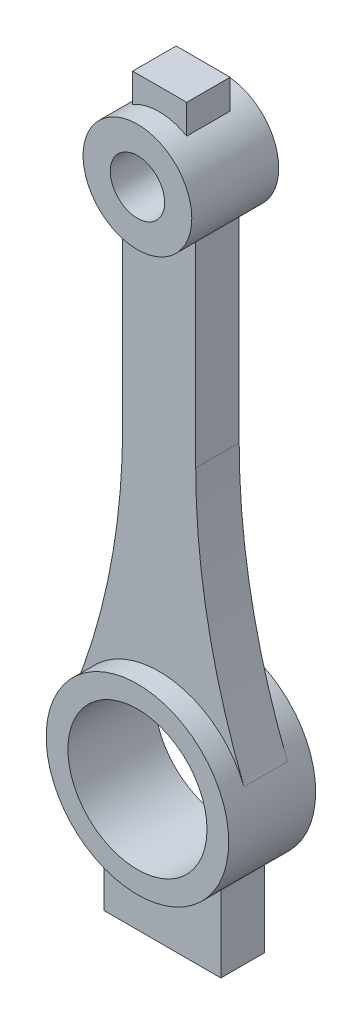
SolidWorks part; units mm, degrees
ref_plane "Front Plane" through (0, 0, 0) normal (0, 0, 1) x (1, 0, 0)
ref_plane "Top Plane" through (0, 0, 0) normal (0, 1, 0) x (1, 0, 0)
ref_plane "Right Plane" through (0, 0, 0) normal (1, 0, 0) x (0, 0, -1)
sketch "Sketch2" plane through (0, 0, 0) normal (0, 0, 1) x (1, 0, 0)
  line L0 (-12.6446, -60.5767) -> (-12.6446, -76.8054)
  line L1 (-12.6446, -76.8054) -> (14.1853, -76.8054)
  line L2 (14.1853, -76.8054) -> (14.1853, -59.2951)
  line L4 (-6.1031, 87.0985) -> (-6.1031, 93.7148)
  line L5 (-6.1031, 93.7148) -> (6.3307, 93.7148)
  line L6 (6.3307, 86.968) -> (6.3307, 93.7148)
  line L7 (-8.4014, 66.9341) -> (-8.4014, 21.9341)
  line L8 (8.4014, 66.9341) -> (8.4014, 21.9341)
  circle A0 centre (0, -43.8103) radius 16
  circle A1 centre (0, -43.8103) radius 21
  circle A3 centre (0, 76.1897) radius 6.25
  circle A4 centre (0, 76.1897) radius 12.5
  arc A5 (-8.4014, 21.9341) -> (-19.5123, -36.0469) centre (-165.2413, 21.9341) cw
  arc A6 (8.4014, 21.9341) -> (19.5123, -36.0469) centre (165.2413, 21.9341) ccw
  point P5 (0, 0)
  dimension "D1" = 32
  dimension "D2" = 42
  dimension "D3" = 12.5
  dimension "D4" = 25
  dimension "D5" = 120
  dimension "D6" = 45
extrude "Boss-Extrude1" add sketch "Sketch2" against normal mid plane 20 contours A1 A0 | A4 A3 region at (-19.6504, -49.3119, 0) region at (-12.0683, 77.5653, 0)
extrude "Boss-Extrude2" add sketch "Sketch2<3>" along normal mid plane 10 contours A6 L8 A4 L7 A5 A1 | A4 L6 L5 L4 | A1 L0 L1 L2 region at (0.9589, -69.9544, 0) region at (0, 15.2399, 0) region at (0.1367, 90.9122, 0)
sketch "Sketch2<3>" plane through (0, 0, 0) normal (0, 0, 1) x (1, 0, 0) same geometry as "Sketch2"
